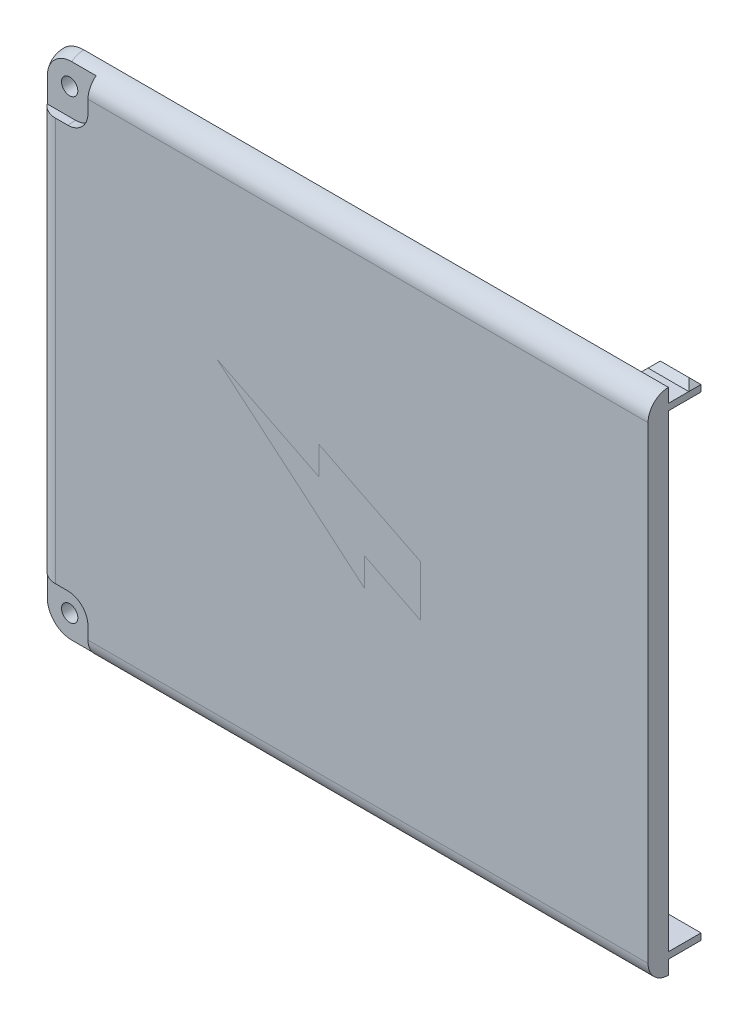
SolidWorks part; units mm, degrees
ref_plane "Front" through (0, 0, 0) normal (0, 0, 1) x (1, 0, 0)
ref_plane "Top" through (0, 0, 0) normal (0, 1, 0) x (1, 0, 0)
ref_plane "Right" through (0, 0, 0) normal (1, 0, 0) x (0, 0, -1)
sketch "Sketch1" plane through (0, 0, 0) normal (0, 0, 1) x (1, 0, 0)
  line L7 (145.5, 120) -> (145.5, -5)
  line L9 (145.5, -5) -> (2, -5)
  line L10 (-5, 2) -> (-5, 113)
  line L11 (2, 120) -> (145.5, 120)
  line L12 (145.5, -5) -> (2, -5)
  line L13 (-5, 2) -> (-5, 113)
  line L14 (2, 120) -> (145.5, 120)
  arc A6 (-5, 2) -> (2, -5) centre (2, 2) ccw
  arc A7 (2, 120) -> (-5, 113) centre (2, 113) ccw
  arc A8 (-5, 2) -> (2, -5) centre (2, 2) ccw
  arc A9 (2, 120) -> (-5, 113) centre (2, 113) ccw
  dimension "D1" = 0
extrude "Boss-Extrude1" add sketch "Sketch1" along normal blind 5
fillet "Fillet1" radius 5 5 edges at (73.75, -5, 5) (-2.9497, -2.9497, 5) (-5, 57.5, 5) (-2.9497, 117.9497, 5) (73.75, 120, 5)
ref_plane "Plane1" through (0, 115, 0) normal (0, 1, 0) x (1, 0, 0)
ref_plane "Plane2" through (0, 57.5, 0) normal (0, 1, 0) x (1, 0, 0)
sketch "Sketch2" plane through (0, 0, 5) normal (0, 0, 1) x (1, 0, 0)
  circle A0 centre (1.5, 113.5) radius 2
  circle A1 centre (1.5, 1.5) radius 2
  dimension "D1" = 4
extrude "Cut-Extrude1" cut sketch "Sketch2" against normal through all
sketch "Sketch3" plane through (0, 0, 0) normal (0, 0, -1) x (-1, 0, 0)
  line L5 (-18, 115) -> (0, 97)
  line L6 (-18, 0) -> (0, 18)
  line L9 (-140.5, 0) -> (-2, 0)
  line L10 (0, 2) -> (0, 113)
  line L11 (-2, 115) -> (-140.5, 115)
  line L12 (-140.5, 115) -> (-140.5, 0)
  line L13 (-140.5, 0) -> (-2, 0)
  line L14 (0, 2) -> (0, 113)
  line L15 (-2, 115) -> (-140.5, 115)
  line L16 (-140.5, 115) -> (-140.5, 0)
  arc A4 (-2, 0) -> (0, 2) centre (-2, 2) ccw
  arc A5 (0, 113) -> (-2, 115) centre (-2, 113) ccw
  arc A6 (-2, 0) -> (0, 2) centre (-2, 2) ccw
  arc A7 (0, 113) -> (-2, 115) centre (-2, 113) ccw
  dimension "D2" = 18
  dimension "D3" = 18
  dimension "D1" = 5
extrude "Cut-Extrude2" cut sketch "Sketch3" against normal blind 2 contours L15 L16 L13 L6 L14 L5 region at (71.5647, 57.5, 0)
sketch "Sketch4" plane through (0, 0, 5) normal (0, 0, 1) x (1, 0, 0)
  line L0 (145.5, 120) -> (2, 120) construction
  line L1 (-5, 107) -> (3, 107)
  line L2 (-5, 107) -> (-5, 120)
  line L3 (-5, 120) -> (8, 120)
  line L4 (8, 112) -> (8, 120)
  line L5 (-5, 113) -> (-5, 2) construction
  arc A0 (3, 107) -> (8, 112) centre (3, 112) ccw
  point P4 (1.5, 120)
  point P9 (1.5, 113.5)
  dimension "D1" = 5
extrude "Cut-Extrude3" cut sketch "Sketch4" against normal blind 2
mirror "Mirror1" about plane through (0, 57.5, 0) normal (0, 1, 0) of "Cut-Extrude3"
sketch "Sketch5" plane through (0, 0, 5) normal (0, 0, 1) x (1, 0, 0)
  circle A0 centre (1.5, 113.5) radius 4
  circle A1 centre (1.5, 1.5) radius 4
  dimension "D1" = 8
extrude "Cut-Extrude4" [suppressed] cut sketch "Sketch5" against normal blind 2
sketch "Sketch6" plane through (0, 0, 5) normal (0, 0, 1) x (1, 0, 0)
  line L0 (-5, 113) -> (-5, 2) construction
  line L1 (-5, -5) -> (145.5, -5) construction
  line L2 (-5, -5) -> (-5, 120) construction
  line L3 (-5, 120) -> (145.5, 120) construction
  line L4 (145.5, -5) -> (145.5, 120) construction
  line L5 (-5, -5) -> (145.5, 120) construction
  line L6 (-5, 120) -> (145.5, -5) construction
  line L7 (2, -5) -> (145.5, -5) construction
  line L8 (89.6598, 57.5) -> (89.6598, 45)
  line L9 (89.6598, 45) -> (75.8402, 51.9098)
  line L10 (75.8402, 51.9098) -> (75.8402, 45)
  line L11 (75.8402, 45) -> (39.6598, 75.5902)
  line L13 (64.6598, 57.5) -> (64.6598, 70) construction
  line L14 (64.6598, 70) -> (89.6598, 57.5)
  line L15 (64.6598, 70) -> (89.6598, 70) construction
  line L16 (89.6598, 70) -> (89.6598, 45) construction
  line L17 (64.6598, 57.5) -> (75.8402, 51.9098) construction
  line L18 (64.6598, 70) -> (64.6598, 63.0902)
  line L19 (64.6598, 63.0902) -> (39.6598, 75.5902)
  line L20 (64.6598, 57.5) -> (70.25, 57.5) construction
  line L21 (70.25, 57.5) -> (70.25, 54.7049) construction
  line L22 (64.6598, 70) -> (64.6598, 75.5902) construction
  line L23 (64.6598, 75.5902) -> (39.6598, 75.5902) construction
  point P0 (70.25, 57.5)
  point P22 (70.25, 54.7049)
  dimension "D1" = 50
extrude "Cut-Extrude5" cut sketch "Sketch6" against normal blind 1
sketch "Sketch7" plane through (0, 0, 4) normal (0, 0, 1) x (1, 0, 0)
  line L7 (89.6598, 57.5) -> (64.6598, 70)
  line L8 (64.6598, 70) -> (64.6598, 63.0902)
  line L9 (64.6598, 63.0902) -> (39.6598, 75.5902)
  line L10 (39.6598, 75.5902) -> (75.8402, 45)
  line L11 (75.8402, 45) -> (75.8402, 51.9098)
  line L12 (75.8402, 51.9098) -> (89.6598, 45)
  line L13 (89.6598, 45) -> (89.6598, 57.5)
  line L14 (89.6598, 57.5) -> (64.6598, 70)
  line L15 (64.6598, 70) -> (64.6598, 63.0902)
  line L16 (64.6598, 63.0902) -> (39.6598, 75.5902)
  line L17 (39.6598, 75.5902) -> (75.8402, 45)
  line L18 (75.8402, 45) -> (75.8402, 51.9098)
  line L19 (75.8402, 51.9098) -> (89.6598, 45)
  line L20 (89.6598, 45) -> (89.6598, 57.5)
  dimension "D1" = 0
extrude "Boss-Extrude2" add sketch "Sketch7" along normal up to surface (1 mm away) separate body up to face at (71.4256, 58.2986, 5)
sketch "Sketch8" plane through (0, 0, 0) normal (0, 0, -1) x (-1, 0, 0)
  line L0 (-145.5, -5) -> (-145.5, 120) construction
  line L1 (-145.5, 116.6) -> (-135.5, 116.6)
  line L2 (-145.5, 116.6) -> (-145.5, 115)
  line L3 (-145.5, 115) -> (-135.5, 115)
  line L4 (-135.5, 116.6) -> (-135.5, 115)
  line L5 (-18, 115) -> (-140.5, 115) construction
  point P5 (-145.5, 118.7342)
  point P8 (-126.873, 115)
  point P11 (-130.1897, 117.4975)
  dimension "D1" = 1.6
  dimension "D2" = 10
extrude "Boss-Extrude3" add sketch "Sketch8" along normal blind 8
sketch "Sketch9" plane through (0, 116.6, 0) normal (0, 1, 0) x (1, 0, 0)
  line L0 (145.5, 8) -> (145.5, 0) construction
  line L1 (135.5, 8) -> (145.5, 8)
  line L2 (135.5, 8) -> (135.5, 5)
  line L3 (135.5, 5) -> (145.5, 5)
  line L4 (145.5, 8) -> (145.5, 5)
  dimension "D1" = 3
extrude "Boss-Extrude4" add sketch "Sketch9" along normal blind 1.5 draft 45
mirror "Mirror2" about plane through (0, 57.5, 0) normal (0, 1, 0) of "Boss-Extrude4", "Boss-Extrude3"
